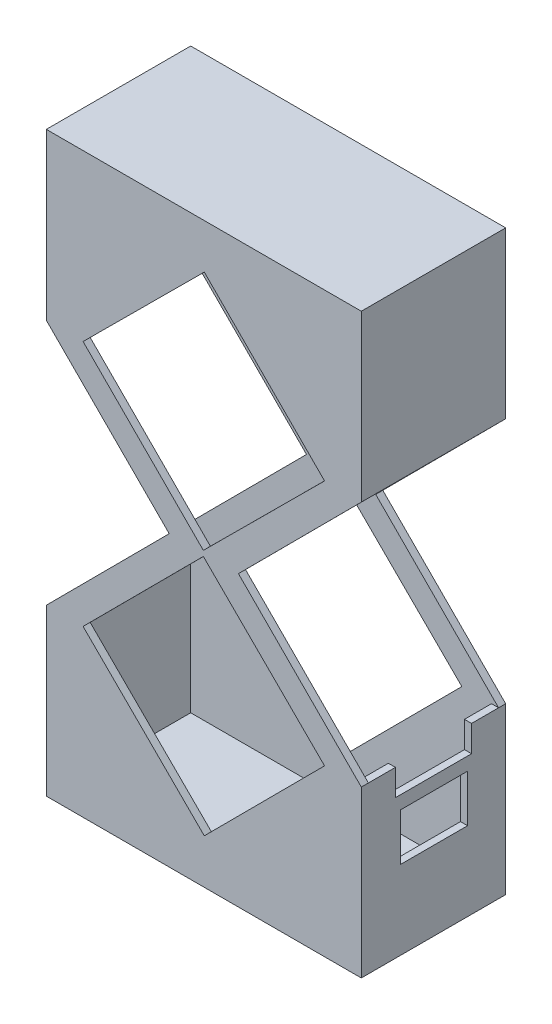
SolidWorks part; units mm, degrees
ref_plane "前视基准面" through (0, 0, 0) normal (0, 0, 1) x (1, 0, 0)
ref_plane "上视基准面" through (0, 0, 0) normal (0, 1, 0) x (1, 0, 0)
ref_plane "右视基准面" through (0, 0, 0) normal (1, 0, 0) x (0, 0, -1)
other "Configuration Table"
sketch "草图1" plane through (0, 0, 0) normal (0, 1, 0) x (1, 0, 0)
  line L1 (-60, 27.5) -> (60, 27.5)
  line L2 (-60, 27.5) -> (-60, -27.5)
  line L3 (-60, -27.5) -> (60, -27.5)
  line L4 (60, 27.5) -> (60, -27.5)
  line L5 (-60, 27.5) -> (60, -27.5) construction
  line L6 (-60, -27.5) -> (60, 27.5) construction
  point P0 (0, 0)
  dimension "D1" = 120
  dimension "D2" = 55
  dimension "D3" = 0
ref_plane "基准面1" through (0, 0, -27.5) normal (0, 0, 1) x (1, 0, 0)
sketch "草图2" plane through (0, 0, -27.5) normal (0, 0, 1) x (1, 0, 0)
  line L0 (-60, 110) -> (60, 110) construction
  line L1 (60, 0) -> (-60, 0)
  line L2 (60, 157) -> (60, 220)
  line L3 (60, 220) -> (-60, 220)
  line L4 (-60, 0) -> (-60, 63)
  line L7 (0, 220) -> (0, 0) construction
  line L14 (0, 157) -> (-46, 157)
  line L15 (0, 203) -> (-46, 157) construction
  line L16 (46, 157) -> (0.1819, 202.9996)
  line L17 (46, 157) -> (-0.1819, 111.0004)
  line L18 (0.1819, 202.9996) -> (-46, 157)
  line L19 (-0.1819, 111.0004) -> (-46, 157)
  line L20 (46, 157) -> (-46, 157) construction
  line L21 (0.1819, 202.9996) -> (-0.1819, 111.0004) construction
  line L22 (0.1819, 17.0004) -> (-46, 63)
  line L23 (-0.1819, 108.9996) -> (-46, 63)
  line L24 (46, 63) -> (-0.1819, 108.9996)
  line L25 (46, 63) -> (0.1819, 17.0004)
  line L26 (-46, 157) -> (-60, 157) construction
  line L27 (46, 157) -> (60, 157) construction
  line L28 (-60, 157) -> (-13.1855, 110)
  line L29 (60, 157) -> (13.1855, 110)
  line L30 (60, 63) -> (13.1855, 110)
  line L31 (-60, 63) -> (-13.1855, 110)
  line L32 (60, 63) -> (60, 0)
  line L33 (-60, 157) -> (-60, 220)
  line L34 (-57.3, 63) -> (-57.3, 2.7)
  line L35 (-57.3, 2.7) -> (57.3, 2.7)
  line L36 (57.3, 2.7) -> (57.3, 63)
  line L37 (-57.3, 63) -> (-60, 63)
  line L38 (57.3, 63) -> (60, 63)
  line L39 (-57.3, 217.3) -> (57.3, 217.3)
  line L40 (-57.3, 157) -> (-57.3, 217.3)
  line L41 (-57.3, 157) -> (-60, 157)
  line L42 (57.3, 217.3) -> (57.3, 157)
  line L43 (57.3, 157) -> (60, 157)
  line L44 (-60, 157) -> (-57.3, 157)
  line L45 (-57.3, 217.3) -> (57.3, 217.3)
  line L46 (57.3, 217.3) -> (57.3, 157)
  line L47 (60, 157) -> (60, 220)
  line L48 (-60, 220) -> (60, 220)
  line L49 (-60, 220) -> (-60, 157)
  line L50 (-57.3, 157) -> (-57.3, 217.3)
  point P9 (0, 157)
  point P10 (0, 67.8137)
  point P15 (0, 157)
  point P16 (0, 110)
  point P17 (0, 60)
  point P18 (-23, 180)
  point P20 (0, 203)
  point P34 (-60, 157)
  point P35 (-60, 63)
  point P36 (60, 63)
  point P37 (60, 157)
  point P41 (-60, 157)
  dimension "D1" = 120
  dimension "D2" = 220
  dimension "D3" = 110
  dimension "D4" = 46
  dimension "D5" = 0.1819
  dimension "D6" = 47
  dimension "D7" = 50
  dimension "D8" = 67.8137
  dimension "D9" = 2.7
  dimension "D10" = 46
  dimension "D11" = 2.7
  dimension "D12" = 2.7
ref_plane "基准面2" through (-60, 0, 0) normal (1, 0, 0) x (0, 0, -1)
extrude "凸台-拉伸1" add sketch "草图2" along normal blind 55 contours L42 L43 L2 L3 L33 L41 L40 L39 region at (58.65, 158.3553, -27.5)
extrude "凸台-拉伸2" add sketch "草图2<7>" along normal blind 55 separate body contours L38 L36 L35 L34 L37 L4 L1 L32 region at (0, 1.3553, -27.5)
sketch "草图2<7>" plane through (0, 0, -27.5) normal (0, 0, 1) x (1, 0, 0) same geometry as "草图2"
extrude "凸台-拉伸3" add sketch "草图2<8>" along normal blind 2.7 contours L43 L42 L39 L40 L41 L28 L31 L37 L34 L35 L36 L38 L30 L29 L17 L19 L18 L16 L24 L25 L22 L23 region at (0, 110, -27.5)
sketch "草图2<8>" plane through (0, 0, -27.5) normal (0, 0, 1) x (1, 0, 0) same geometry as "草图2"
extrude "凸台-拉伸4" add sketch "草图2<9>" along normal blind 2.7 from offset 52.3 contours L43 L42 L39 L40 L41 L28 L31 L37 L34 L35 L36 L38 L30 L29 L17 L19 L18 L16 L24 L25 L22 L23 region at (0, 110, -27.5)
sketch "草图2<9>" plane through (0, 0, -27.5) normal (0, 0, 1) x (1, 0, 0) same geometry as "草图2"
sketch "草图4" plane through (60, 0, 0) normal (1, 0, 0) x (0, 0, -1)
  line L0 (-27.5, 63) -> (-27.5, 0) construction
  line L1 (-12.5, 48) -> (13, 48)
  line L2 (-12.5, 48) -> (-12.5, 30)
  line L3 (-12.5, 30) -> (13, 30)
  line L4 (13, 48) -> (13, 30)
  line L5 (-24.8, 63) -> (24.8, 63) construction
  line L8 (-14.5, 63) -> (14.5, 63)
  line L9 (-14.5, 63) -> (-14.5, 53)
  line L10 (-14.5, 53) -> (14.5, 53)
  line L11 (14.5, 63) -> (14.5, 53)
  dimension "D1" = 25.5
  dimension "D2" = 18
  dimension "D3" = 15
  dimension "D4" = 15
  dimension "D5" = 29
  dimension "D6" = 10
  dimension "D7" = 13
extrude "切除-拉伸1" cut sketch "草图4" against normal blind 2.7
